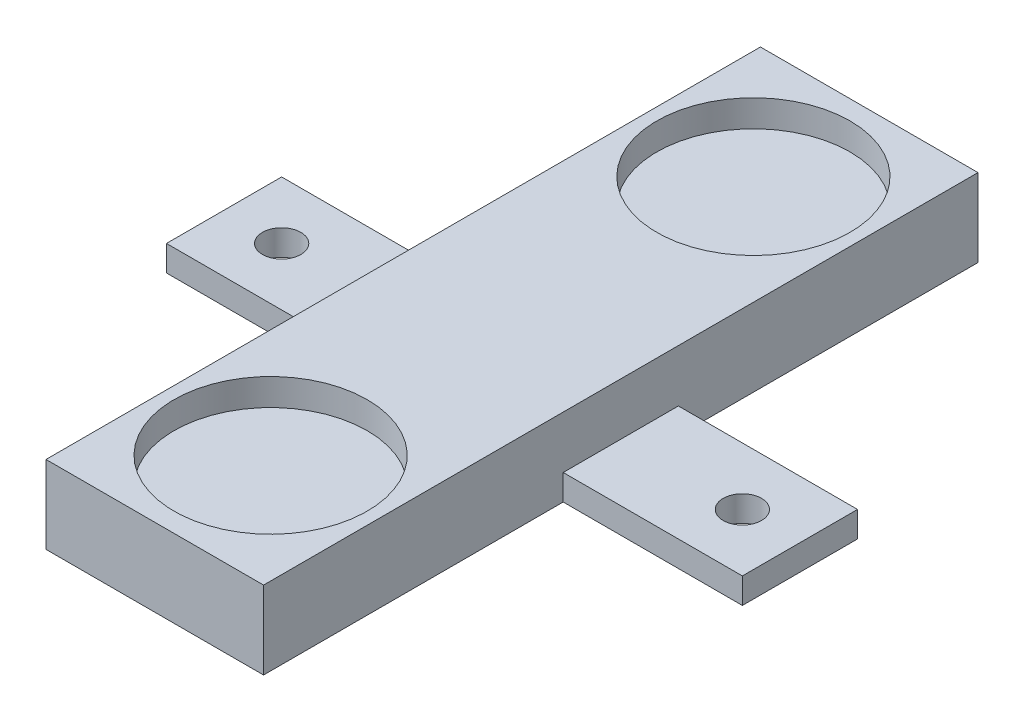
SolidWorks part; units mm, degrees
ref_plane "Front Plane" through (0, 0, 0) normal (0, 0, 1) x (1, 0, 0)
ref_plane "Top Plane" through (0, 0, 0) normal (0, 1, 0) x (1, 0, 0)
ref_plane "Right Plane" through (0, 0, 0) normal (1, 0, 0) x (0, 0, -1)
sketch "Sketch1" plane through (0, 0, 0) normal (0, 1, 0) x (1, 0, 0)
  line L0 (0, 27.9125) -> (0, 0) construction
  line L1 (-8.5, 27.9125) -> (8.5, 27.9125)
  line L2 (-8.5, 27.9125) -> (-8.5, -27.9125)
  line L3 (-8.5, -27.9125) -> (8.5, -27.9125)
  line L4 (8.5, 27.9125) -> (8.5, -27.9125)
  line L5 (-8.5, 0) -> (0, 0) construction
  line L6 (0, 18.8625) -> (0, -18.8625) construction
  line L7 (-18, 0) -> (18, 0) construction
  line L8 (-8.5, 4.5) -> (-22.5, 4.5)
  line L9 (-8.5, 4.5) -> (-8.5, -4.5)
  line L10 (-8.5, -4.5) -> (-22.5, -4.5)
  line L11 (-22.5, 4.5) -> (-22.5, -4.5)
  line L12 (8.5, 4.5) -> (22.5, 4.5)
  line L13 (8.5, 4.5) -> (8.5, -4.5)
  line L14 (8.5, -4.5) -> (22.5, -4.5)
  line L15 (22.5, 4.5) -> (22.5, -4.5)
  circle A0 centre (0, 18.8625) radius 7.55
  circle A1 centre (0, -18.8625) radius 7.55
  circle A2 centre (-18, 0) radius 1.5
  circle A3 centre (18, 0) radius 1.5
  point P24 (0, 0)
  point P28 (-22.5, 0)
  dimension "D3" = 15.1
  dimension "D7" = 3
  dimension "D1" = 55.825
  dimension "D2" = 17
  dimension "D4" = 37.725
  dimension "D5" = 9.05
  dimension "D6" = 36
  dimension "D8" = 4.5
  dimension "D9" = 9
extrude "Boss-Extrude1" add sketch "Sketch1" along normal blind 2 contours L4 L1 L2 L3 A1 A0 | L15 L12 L4 L14 A3 | L8 L11 L10 L2 A2 | A1 | A0 region at (0, 0, 0) region at (-15.3514, 0, 0) region at (15.3514, 0, 0) region at (0, 0, -18.8625) region at (0, 0, 18.8625)
extrude "Boss-Extrude2" add sketch "Sketch1<4>" along normal blind 1.988 from surface contours L4 L1 L2 L3 A1 A0 | A1 | A0 region at (0, 0, 0) region at (0, 0, -18.8625) region at (0, 0, 18.8625) starting at face at (0, 2, 0)
sketch "Sketch1<4>" plane through (0, 0, 0) normal (0, 1, 0) x (1, 0, 0) same geometry as "Sketch1"
extrude "Boss-Extrude3" add sketch "Sketch1<5>" along normal blind 2.1 from surface contours L4 L1 L2 L3 A1 A0 region at (0, 0, 0) starting at face at (0, 3.988, 0)
sketch "Sketch1<5>" plane through (0, 0, 0) normal (0, 1, 0) x (1, 0, 0) same geometry as "Sketch1"
equation "\"D1@Boss-Extrude2\"=\"bottomThickness\"-2.1mm-1.5mm"
equation "\"bottomThickness\"= .220in"
equation "\"wallThickness\"= .118in"
